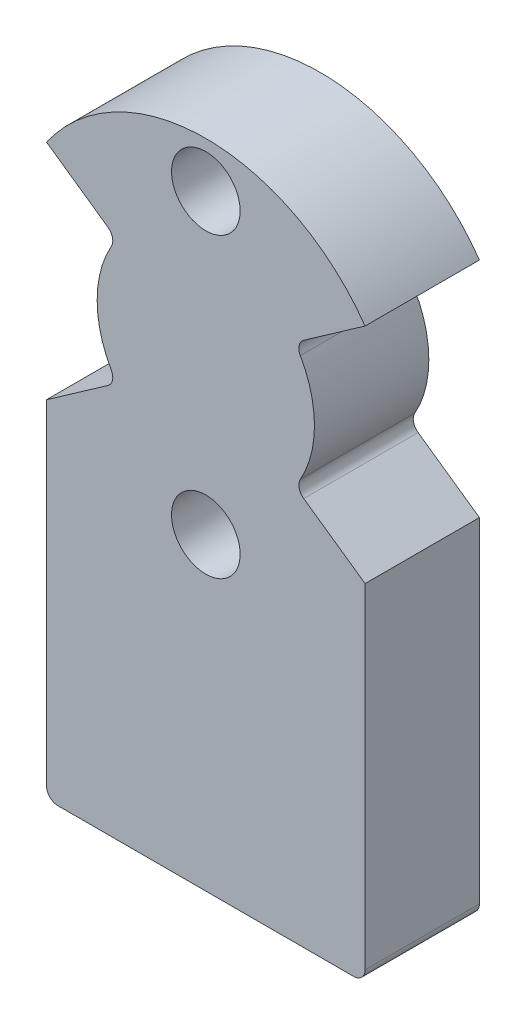
SolidWorks part; units mm, degrees
material "Thornel Mat VMA"
ref_plane "前视基准面" through (0, 0, 0) normal (0, 0, 1) x (1, 0, 0)
ref_plane "上视基准面" through (0, 0, 0) normal (0, 1, 0) x (1, 0, 0)
ref_plane "右视基准面" through (0, 0, 0) normal (1, 0, 0) x (0, 0, -1)
sketch "草图1" plane through (0, 0, 0) normal (0, 0, 1) x (1, 0, 0)
  circle A0 centre (0, 0) radius 8.5
  dimension "D1" = 17
extrude "凸台-拉伸1" add sketch "草图1" along normal blind 5
sketch "草图2" plane through (0, 0, 5) normal (0, 0, 1) x (1, 0, 0)
  circle A0 centre (0, 0) radius 6.5 construction
  circle A1 centre (0, 6.5) radius 1.5
  circle A2 centre (0, -6.5) radius 1.5
  dimension "D1" = 13
  dimension "D2" = 3
extrude "切除-拉伸1" cut sketch "草图2" against normal blind 5
sketch "草图3" plane through (0, 0, 0) normal (0, 0, -1) x (-1, 0, 0)
  line L0 (0, 0) -> (11.6987, 0) construction
  line L1 (0, 0) -> (6.9628, 4.8754)
  line L2 (0, 0) -> (6.9628, -4.8754)
  circle A0 centre (0, 0) radius 4.75
  circle A1 centre (0, 0) radius 8.5
  circle M17 centre (0, 0) radius 8.5
  dimension "D1" = 9.5
  dimension "D2" = 17
  dimension "D3" = 35
  dimension "D4" = 35
extrude "切除-拉伸2" cut sketch "草图3" against normal through all contours A0 L0 A1 L1 | L0 A0 L2 M17 region at (-6.3867, 2.0137, 0) region at (-6.3867, -2.0137, 0)
mirror "镜向1" about plane through (0, 0, 0) normal (1, 0, 0) of "切除-拉伸2"
sketch "草图4" plane through (0, 0, 0) normal (0, 0, -1) x (-1, 0, 0)
  line L2 (-6.9628, 4.8754) -> (-6.9628, -20)
  line L3 (-6.9628, -20) -> (6.9628, -20)
  line L4 (6.9628, 4.8754) -> (6.9628, -20)
  line L5 (-2.7947, 8.0274) -> (6.9628, -20) construction
  line L6 (-6.9628, -20) -> (2.7947, 8.0274) construction
  circle A0 centre (0, 0) radius 8.5
  arc M9 (-6.9628, -4.8754) -> (6.9628, -4.8754) centre (0, 0) ccw
  dimension "D1" = 17
  dimension "D2" = 13.9256
  dimension "D3" = 20
extrude "凸台-拉伸2" add sketch "草图4" against normal blind 5 separate body contours L4 L2 L3 M9 region at (0, -13.6669, 0)
combine bodies "组合1" operation type add bodies to combine 109 110 110
fillet "圆角1" radius 0.5 4 edges at (-3.891, -2.7245, 2.5) (-3.891, 2.7245, 2.5) (3.891, 2.7245, 2.5) (3.891, -2.7245, 2.5)
fillet "圆角2" radius 0.5 2 edges at (6.9628, -20, 2.5) (-6.9628, -20, 2.5)
